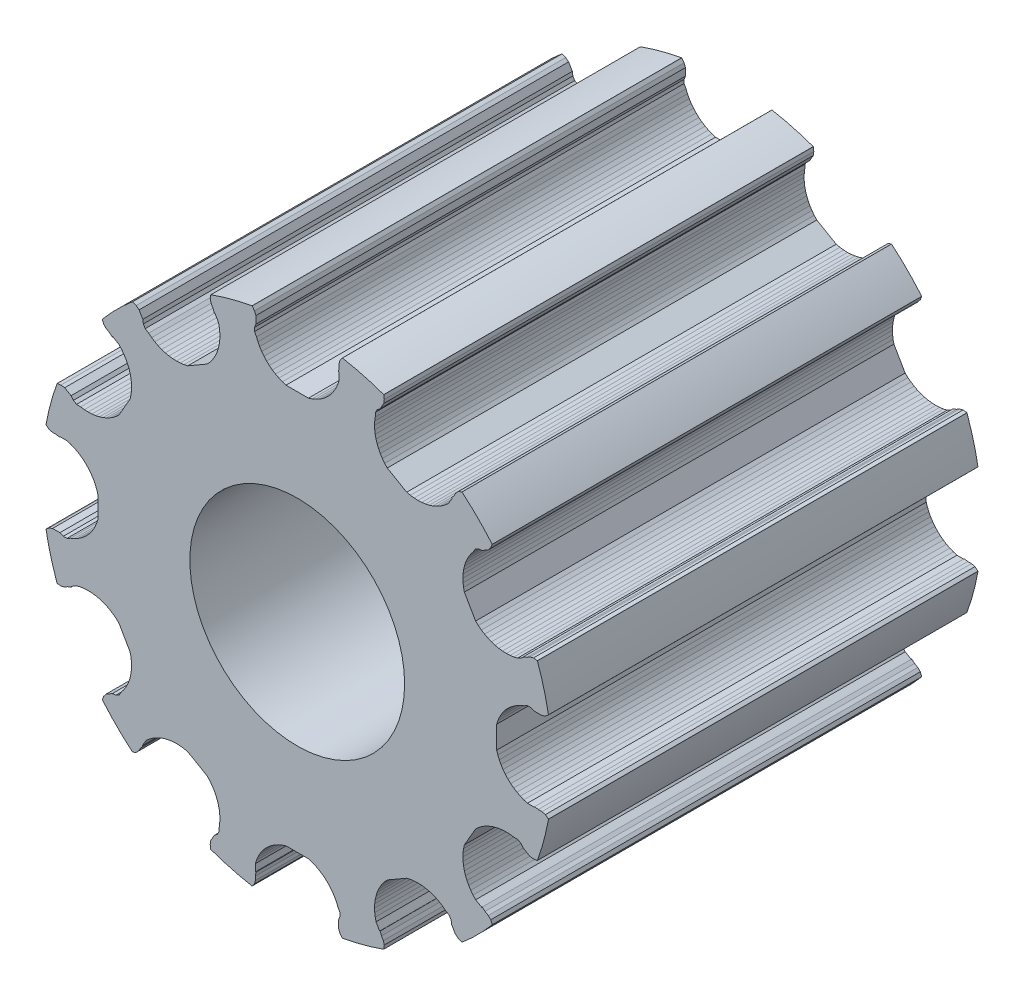
SolidWorks part; units mm, degrees
ref_plane "Front Plane" through (0, 0, 0) normal (0, 0, 1) x (1, 0, 0)
ref_plane "Top Plane" through (0, 0, 0) normal (0, 1, 0) x (1, 0, 0)
ref_plane "Right Plane" through (0, 0, 0) normal (1, 0, 0) x (0, 0, -1)
sketch "Sketch1" plane through (0, 0, 0) normal (0, 0, 1) x (1, 0, 0)
  circle A0 centre (0, 0) radius 3.5657
  circle A1 centre (0, 0) radius 1.5
extrude "Boss-Extrude1" add sketch "Sketch1" along normal blind 6
sketch "Sketch2" plane through (0, 0, 0) normal (0, 0, 1) x (1, 0, 0)
  line L0 (4.0657, 1) -> (3.5657, 1)
  line L1 (3.5657, 1) -> (3.5657, 0.77)
  line L2 (3.5657, 0.77) -> (3.5657, 0.7184)
  line L3 (3.5657, 0.7184) -> (3.5391, 0.6703)
  line L4 (3.5391, 0.6703) -> (3.5075, 0.629)
  line L5 (3.5075, 0.629) -> (3.4664, 0.5972)
  line L6 (3.4664, 0.5972) -> (3.4184, 0.5771)
  line L7 (3.4184, 0.5771) -> (3.3668, 0.5771)
  line L8 (3.3668, 0.5771) -> (3.3152, 0.5771)
  line L9 (3.3152, 0.5771) -> (3.267, 0.596)
  line L10 (3.267, 0.596) -> (3.2154, 0.596)
  line L11 (3.2154, 0.596) -> (3.1649, 0.5689)
  line L12 (3.1649, 0.5689) -> (3.1161, 0.5488)
  line L13 (3.1161, 0.5488) -> (3.0691, 0.5245)
  line L14 (3.0691, 0.5245) -> (3.0245, 0.4961)
  line L15 (3.0245, 0.4961) -> (2.9825, 0.464)
  line L16 (2.9825, 0.464) -> (2.9435, 0.4283)
  line L17 (2.9435, 0.4283) -> (2.9077, 0.3894)
  line L18 (2.9077, 0.3894) -> (2.8755, 0.3475)
  line L19 (2.8755, 0.3475) -> (2.847, 0.3029)
  line L20 (2.847, 0.3029) -> (2.8226, 0.2561)
  line L21 (2.8226, 0.2561) -> (2.8023, 0.2072)
  line L22 (2.8023, 0.2072) -> (2.7864, 0.1568)
  line L23 (2.7864, 0.1568) -> (2.7864, 0.1052)
  line L24 (2.7864, 0.1052) -> (2.7864, 0.0528)
  line L25 (2.7864, 0.0528) -> (2.7864, 0)
  line L26 (2.7864, 0) -> (2.7864, -0.0528)
  line L27 (2.7864, -0.0528) -> (2.7864, -0.1052)
  line L28 (2.7864, -0.1052) -> (2.7864, -0.1568)
  line L29 (2.7864, -0.1568) -> (2.8023, -0.2072)
  line L30 (2.8023, -0.2072) -> (2.8226, -0.2561)
  line L31 (2.8226, -0.2561) -> (2.847, -0.3029)
  line L32 (2.847, -0.3029) -> (2.8755, -0.3475)
  line L33 (2.8755, -0.3475) -> (2.9077, -0.3894)
  line L34 (2.9077, -0.3894) -> (2.9435, -0.4283)
  line L35 (2.9435, -0.4283) -> (2.9825, -0.464)
  line L36 (2.9825, -0.464) -> (3.0245, -0.4961)
  line L37 (3.0245, -0.4961) -> (3.0691, -0.5245)
  line L38 (3.0691, -0.5245) -> (3.1161, -0.5488)
  line L39 (3.1161, -0.5488) -> (3.1649, -0.5689)
  line L40 (3.1649, -0.5689) -> (3.2154, -0.5847)
  line L41 (3.2154, -0.5847) -> (3.3152, -0.5847)
  line L42 (3.3152, -0.5847) -> (3.3152, -0.5765)
  line L43 (3.3152, -0.5765) -> (3.3668, -0.5847)
  line L44 (3.3668, -0.5847) -> (3.4184, -0.5847)
  line L45 (3.4184, -0.5847) -> (3.4664, -0.5972)
  line L46 (3.4664, -0.5972) -> (3.5075, -0.629)
  line L47 (3.5075, -0.629) -> (3.5391, -0.6703)
  line L48 (3.5391, -0.6703) -> (3.559, -0.7184)
  line L49 (3.559, -0.7184) -> (3.559, -0.77)
  line L50 (3.559, -0.77) -> (3.559, -1)
  line L51 (3.559, -1) -> (4.0657, -1)
  line L52 (4.0657, -1) -> (4.0657, 1)
extrude "Cut-Extrude2" cut sketch "Sketch2" along normal blind 6.2
ref_axis "Axis1" through (0, 0, -0.3) along (0, 0, 1)
pattern_circular "CirPattern1" count 12 every 30 about axis through (0, 0, -0.3) along (0, 0, 1) of "Cut-Extrude2"
